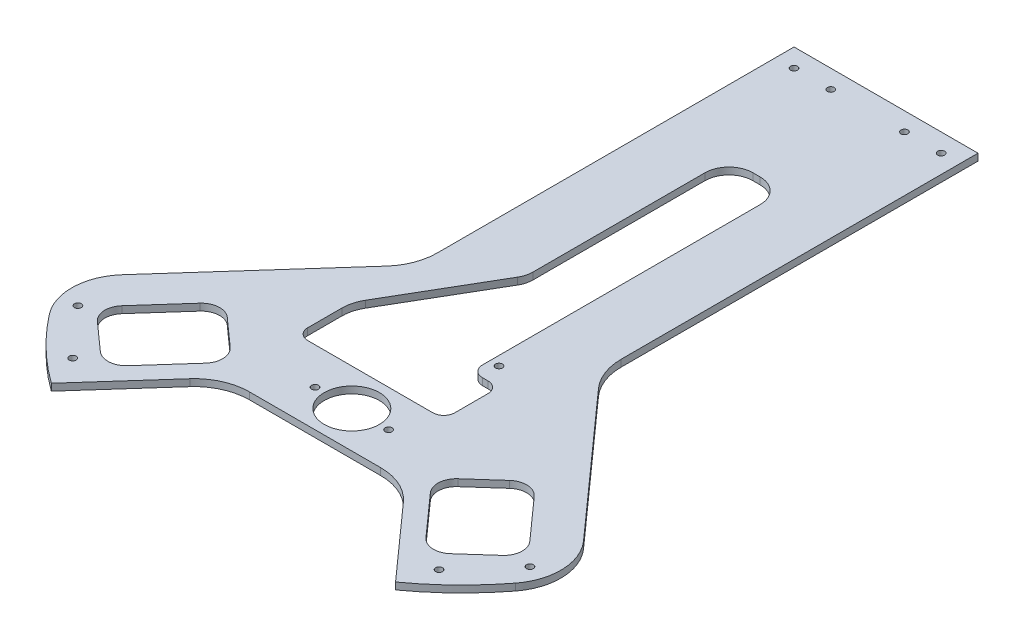
SolidWorks part; units mm, degrees
ref_plane "Front Plane" through (0, 0, 0) normal (0, 0, 1) x (1, 0, 0)
ref_plane "Top Plane" through (0, 0, 0) normal (0, 1, 0) x (1, 0, 0)
ref_plane "Right Plane" through (0, 0, 0) normal (1, 0, 0) x (0, 0, -1)
sketch "Sketch1" plane through (0, 0, 0) normal (0, 1, 0) x (1, 0, 0)
  line L0 (-63.5, 31.75) -> (-178.5164, -97.0677)
  line L1 (-215.9, 31.75) -> (215.9, 31.75)
  line L2 (-215.9, 31.75) -> (-215.9, -31.75)
  line L3 (-215.9, -31.75) -> (215.9, -31.75)
  line L4 (215.9, 31.75) -> (215.9, -31.75)
  line L5 (-215.9, 31.75) -> (215.9, -31.75) construction
  line L6 (-215.9, -31.75) -> (215.9, 31.75) construction
  line L7 (63.5, 31.75) -> (-63.5, 31.75)
  line L8 (63.5, 31.75) -> (63.5, 292.608)
  line L9 (63.5, 292.608) -> (-63.5, 292.608)
  line L10 (-63.5, 31.75) -> (-63.5, 292.608)
  line L11 (0, -31.75) -> (-118.8264, -164.8348)
  line L12 (0, -31.75) -> (118.8264, -164.8348)
  line L13 (63.5, 31.75) -> (178.5164, -97.0677)
  line L14 (-62.3664, -101.6) -> (62.3664, -101.6)
  circle A1 centre (0, 0) radius 25.4 construction
  circle A2 centre (-25.4, 0) radius 2.3813
  circle A3 centre (25.4, 0) radius 2.3812
  circle A4 centre (0, 0) radius 203.2
  circle A5 centre (0, -76.2) radius 25.4 construction
  circle A6 centre (-25.4, -76.2) radius 2.3813
  circle A7 centre (25.4, -76.2) radius 2.3813
  point P0 (0, 0)
  dimension "D5" = 4.7625
  dimension "D6" = 4.7625
  dimension "D7" = 101.6
  dimension "D8" = 50.8
  dimension "D10" = 406.4
  dimension "D14" = 4.7625
  dimension "D15" = 4.7625
  dimension "D16" = 50.8
  dimension "D1" = 431.8
  dimension "D2" = 63.5
  dimension "D3" = 127
  dimension "D4" = 63.5
  dimension "D9" = 260.858
  dimension "D11" = 59.69
  dimension "D12" = 59.69
  dimension "D13" = 76.2
extrude "Boss-Extrude1" add sketch "Sketch1" along normal blind 4.7625 contours L10 L1 L8 L9 | L4 L1 L2 L3 A3 A2 | L0 A4 L11 L3 | L12 A4 L13 L3 | A4 L8 L9 L10 | L11 L14 L12 region at (0, 0, 3.2765) region at (0, 0, -115.8234) region at (-100.5416, 0, 84.5084) region at (0, 0, -246.176) region at (0, 0, 78.3341) region at (100.5416, 0, 84.5084)
sketch "Sketch2" plane through (0, 4.7625, 0) normal (0, 1, 0) x (1, 0, 0)
  line L0 (0, 292.608) -> (0, -101.6) construction
  line L1 (63.5, 292.608) -> (-63.5, 292.608) construction
  line L2 (-62.3664, -101.6) -> (62.3664, -101.6) construction
  circle A0 centre (25.4, 279.908) radius 2.3813
  circle A1 centre (50.8, 279.908) radius 2.3813
  circle A2 centre (-50.8, 279.908) radius 2.3813
  circle A3 centre (-25.4, 279.908) radius 2.3813
  dimension "D3" = 4.7625
  dimension "D4" = 4.7625
  dimension "D1" = 25.4
  dimension "D2" = 50.8
  dimension "D5" = 12.7
  dimension "D6" = 12.7
extrude "Cut-Extrude1" cut sketch "Sketch2" against normal through all
fillet "Fillet1" radius 38.1 4 edges at (63.5, 2.3813, -31.75) (-63.5, 2.3813, -31.75) (62.3664, 2.3813, 101.6) (-62.3664, 2.3813, 101.6)
sketch "Sketch4" plane through (0, 4.7625, 0) normal (0, 1, 0) x (1, 0, 0)
  line L0 (0, 292.608) -> (0, 0) construction
  line L1 (63.5, 292.608) -> (-63.5, 292.608) construction
  line L2 (0, 0) -> (0, -190.5) construction
  line L3 (0, 0) -> (-156.0485, -109.2663) construction
  circle A0 centre (0, 0) radius 190.5 construction
  circle A1 centre (-156.0485, -109.2663) radius 2.3813
  circle A2 centre (-126.4791, -142.4545) radius 2.3813
  circle A3 centre (126.4791, -142.4545) radius 2.3813
  circle A4 centre (156.0485, -109.2663) radius 2.3813
  dimension "D1" = 381
  dimension "D4" = 4.7625
  dimension "D5" = 4.7625
  dimension "D2" = 44.45
  dimension "D3" = 55
extrude "Cut-Extrude3" cut sketch "Sketch4" against normal through all
fillet "Fillet2" radius 38.1 2 edges at (178.5164, 2.3813, 97.0677) (-178.5164, 2.3813, 97.0677)
sketch "Sketch5" plane through (0, 4.7625, 0) normal (0, 1, 0) x (1, 0, 0)
  line L0 (-149.2765, -103.5959) -> (-111.3829, -137.4296)
  line L1 (-149.2765, -103.5959) -> (-106.9843, -56.229)
  line L2 (-111.3829, -137.4296) -> (-69.0908, -90.0627)
  line L3 (-106.9843, -56.229) -> (-69.0908, -90.0627)
  line L8 (-73.7278, -114.3247) -> (-118.8264, -164.8348) construction
  line L9 (0, 292.608) -> (0, -101.6) construction
  line L10 (63.5, 292.608) -> (-63.5, 292.608) construction
  line L11 (106.9843, -56.229) -> (69.0908, -90.0627)
  line L12 (111.3829, -137.4296) -> (69.0908, -90.0627)
  line L13 (149.2765, -103.5959) -> (106.9843, -56.229)
  line L14 (149.2765, -103.5959) -> (111.3829, -137.4296)
  line L15 (-45.3077, -101.6) -> (45.3077, -101.6) construction
  dimension "D1" = 50.8
  dimension "D2" = 12.7
  dimension "D3" = 63.5
  dimension "D4" = 25.4
extrude "Cut-Extrude4" cut sketch "Sketch5" against normal through all
fillet "Fillet3" radius 12.7 8 edges at (111.3829, 2.3813, 137.4296) (69.0908, 2.3813, 90.0627) (106.9843, 2.3813, 56.229) (149.2765, 2.3813, 103.5959) (-69.0908, 2.3813, 90.0627) (-106.9843, 2.3813, 56.229) (-149.2765, 2.3813, 103.5959) (-111.3829, 2.3813, 137.4296)
sketch "Sketch6" plane through (0, 4.7625, 0) normal (0, 1, 0) x (1, 0, 0)
  circle A0 centre (0, -76.2) radius 19.05
  dimension "D1" = 38.1
  dimension "D2" = 76.2
extrude "Cut-Extrude5" cut sketch "Sketch6" against normal through all
sketch "Sketch7" plane through (0, 4.7625, 0) normal (0, 1, 0) x (1, 0, 0)
  line L0 (-45.3077, -101.6) -> (45.3077, -101.6) construction
  line L1 (-19.05, 203.2) -> (19.05, 203.2)
  line L2 (-19.05, 203.2) -> (-19.05, -50.8)
  line L3 (-19.05, -50.8) -> (19.05, -50.8)
  line L4 (19.05, 203.2) -> (19.05, -50.8)
  line L5 (-19.05, 203.2) -> (19.05, -50.8) construction
  line L6 (-19.05, -50.8) -> (19.05, 203.2) construction
  point P0 (0, 76.2)
  point P5 (0, 0)
  dimension "D1" = 38.1
  dimension "D2" = 50.8
  dimension "D3" = 254
extrude "Cut-Extrude6" cut sketch "Sketch7" against normal through all
sketch "Sketch8" plane through (0, 4.7625, 0) normal (0, 1, 0) x (1, 0, 0)
  line L0 (-19.05, -50.8) -> (19.05, -50.8) construction
  line L1 (-63.5, -50.8) -> (38.1, -50.8)
  line L2 (-63.5, -50.8) -> (-63.5, -12.7)
  line L3 (-63.5, -12.7) -> (38.1, -12.7)
  line L4 (38.1, -50.8) -> (38.1, -12.7)
  dimension "D1" = 101.6
  dimension "D2" = 38.1
  dimension "D3" = 38.1
extrude "Cut-Extrude7" cut sketch "Sketch8" against normal through all
sketch "Sketch9" plane through (0, 4.7625, 0) normal (0, 1, 0) x (1, 0, 0)
  line L0 (-63.5, -12.7) -> (-19.05, 63.5)
  line L1 (-19.05, 203.2) -> (-19.05, -12.7) construction
  line L2 (-19.05, 63.5) -> (-19.05, -12.7)
  line L3 (-19.05, -12.7) -> (-63.5, -12.7)
  dimension "D1" = 76.2
extrude "Cut-Extrude8" cut sketch "Sketch9" against normal through all
fillet "Fillet4" radius 25.4 1 edges at (-63.5, 2.3813, 12.7)
fillet "Fillet5" radius 7.62 4 edges at (-63.5, 2.3813, 50.8) (38.1, 2.3813, 50.8) (38.1, 2.3813, 12.7) (19.05, 2.3813, 12.7)
fillet "Fillet8" radius 16.51 3 edges at (-19.05, 2.3813, -203.2) (19.05, 2.3813, -203.2) (-19.05, 2.3813, -63.5)
